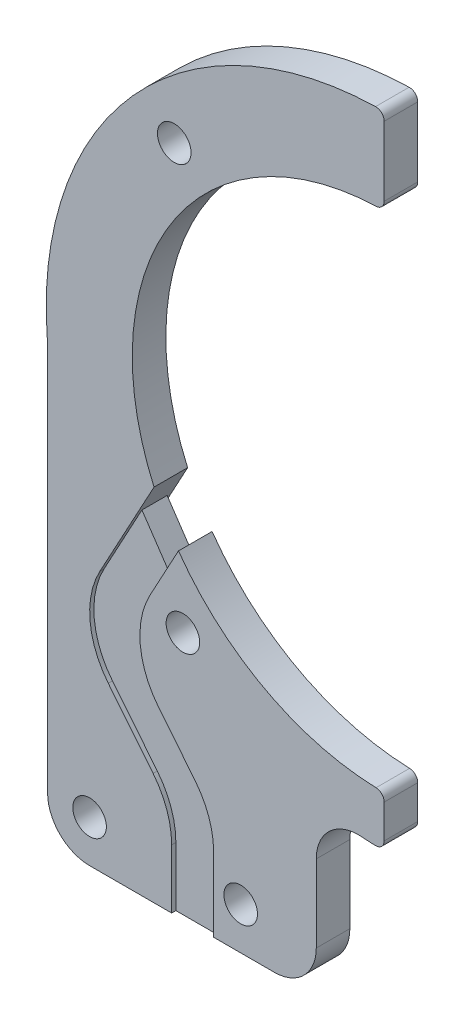
SolidWorks part; units mm, degrees
material "Pine"
ref_plane "Front Plane" through (0, 0, 0) normal (0, 0, 1) x (1, 0, 0)
ref_plane "Top Plane" through (0, 0, 0) normal (0, 1, 0) x (1, 0, 0)
ref_plane "Right Plane" through (0, 0, 0) normal (1, 0, 0) x (0, 0, -1)
sketch "Sketch1" plane through (0, 0, 0) normal (0, 0, 1) x (1, 0, 0)
  line L0 (0, 0) -> (18, 0) construction
  line L1 (18, 0) -> (18, 36.0302) construction
  line L2 (0, 28.9286) -> (0, 0) construction
  line L3 (-5, -5) -> (-5, 46.4286)
  line L4 (-5, -5) -> (27, -5)
  line L5 (27, -5) -> (27, 15)
  line L9 (35.0863, 14.0801) -> (35.0863, 90.3323) construction
  line L10 (27, -5) -> (-5, 46.4286) construction
  line L11 (35.0863, 90.3323) -> (35.0863, 80.0801)
  line L12 (35.0863, 20.0801) -> (35.0863, 14.0801)
  line L14 (18, 0) -> (0, 28.9286) construction
  line L15 (-5, 46.4286) -> (-5, -5) construction
  circle A0 centre (0, 0) radius 2
  circle A1 centre (18, 0) radius 2
  arc A3 (35.0863, 80.0801) -> (35.0863, 20.0801) centre (35.0863, 50.0801) ccw
  arc A4 (35.0863, 90.3323) -> (-5, 46.4286) centre (35.0863, 50.0801) ccw
  arc A5 (27, 15) -> (35.0863, 14.0801) centre (35.0863, 50.0801) ccw
  dimension "D2" = 60
  dimension "D3" = 20
  dimension "D6" = 4
  dimension "D7" = 40.2522
  dimension "D4" = 18
  dimension "D5" = 32
  dimension "D1" = 5
extrude "Boss-Extrude1" add sketch "Sketch1" along normal blind 4
fillet "Fillet10" radius 1 4 edges at (35.0863, 90.3323, 2) (35.0863, 80.0801, 2) (35.0863, 14.0801, 2) (35.0863, 20.0801, 2)
fillet "Fillet11" radius 10 1 edges at (-5, 46.4286, 2)
fillet "Fillet12" radius 5 1 edges at (-5, -5, 2)
fillet "Fillet13" radius 5 1 edges at (27, -5, 2)
fillet "Fillet14" radius 5 1 edges at (27, 15, 2)
sketch "Sketch2" plane through (0, 0, 4) normal (0, 0, 1) x (1, 0, 0)
  line L1 (35.0863, 81.0639) -> (35.0863, 89.3196) construction
  circle A0 centre (10.0863, 74.575) radius 2
  circle A1 centre (11.1178, 24.575) radius 2
  arc A4 (33.9572, 85.0619) -> (33.9572, 15.0983) centre (35.0863, 50.0801) ccw construction
  dimension "D1" = 35
  dimension "D2" = 4
  dimension "D3" = 50
  dimension "D4" = 25
extrude "Cut-Extrude1" cut sketch "Sketch2" against normal blind 20
sketch "Sketch3" plane through (0, 0, 0) normal (0, 0, -1) x (-1, 0, 0)
  line L0 (-14.7773, -5) -> (-14.7773, 7.3179)
  line L1 (0, -5) -> (-22, -5) construction
  line L2 (-14.7773, 7.3179) -> (-4.032, 20.6524)
  line L3 (-4.032, 20.6524) -> (-10.5901, 32.7615)
  line L4 (-9.7773, -5) -> (-9.7773, 5.5541)
  line L5 (-9.7773, 5.5541) -> (1.9496, 20.1067)
  line L6 (1.9496, 20.1067) -> (-7.6776, 37.8831)
  line L7 (1.9496, 20.1067) -> (-6.1934, 35.1426) construction
  line L8 (-14.7773, -5) -> (-9.7773, -5)
  arc A0 (-34.1185, 20.0957) -> (-34.1185, 80.0645) centre (-35.0863, 50.0801) ccw construction
  arc A1 (-10.5901, 32.7615) -> (-7.6776, 37.8831) centre (-35.0863, 50.0801) ccw
  dimension "D1" = 5
  dimension "D2" = 12.1091
  dimension "D3" = 13.3344
  dimension "D4" = 12.3179
  dimension "D5" = 10.5541
  dimension "D6" = 14.5527
extrude "Cut-Extrude2" cut sketch "Sketch3" against normal blind 0.5
fillet "Fillet15" radius 10 4 edges at (9.7773, 5.5541, 0.25) (14.7773, 7.3179, 0.25) (-1.9496, 20.1067, 0.25) (4.032, 20.6524, 0.25)
sketch "Sketch4" plane through (0, 0, 0.5) normal (0, 0, -1) x (-1, 0, 0)
  line L0 (-10.5901, 32.7615) -> (-7.2022, 26.5058) construction
  line L1 (-1.2205, 25.9602) -> (-7.6776, 37.8831) construction
  line L2 (-10.5901, 32.7615) -> (-8.8961, 29.6336)
  line L3 (-5.7384, 34.3023) -> (-7.6776, 37.8831)
  line L4 (-8.8961, 29.6336) -> (-5.7384, 34.3023)
  arc A0 (-10.5901, 32.7615) -> (-7.6776, 37.8831) centre (-35.0863, 50.0801) ccw construction
  arc A1 (-10.5901, 32.7615) -> (-7.6776, 37.8831) centre (-35.0863, 50.0801) ccw
  dimension "D1" = 3.1577
  dimension "D2" = 33.1491
extrude "Cut-Extrude3" cut sketch "Sketch4" against normal through all and the other way through all
ref_plane "Plane1" through (0, 0, 2) normal (0, 0, 1) x (1, 0, 0)
mirror "Mirror1" about plane through (0, 0, 2) normal (0, 0, 1) of "Fillet15", "Cut-Extrude2"
